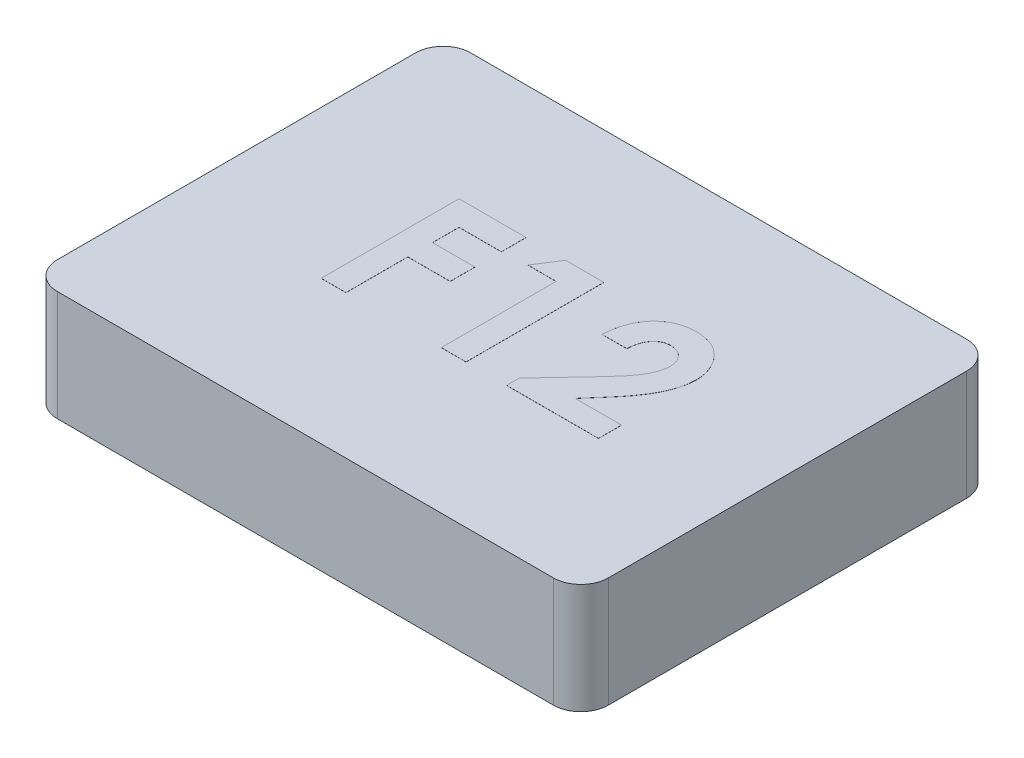
SolidWorks part; units mm, degrees
ref_plane "Front Plane" through (0, 0, 0) normal (0, 0, 1) x (1, 0, 0)
ref_plane "Top Plane" through (0, 0, 0) normal (0, 1, 0) x (1, 0, 0)
ref_plane "Right Plane" through (0, 0, 0) normal (1, 0, 0) x (0, 0, -1)
sketch "Sketch1" plane through (0, 0, 0) normal (0, 1, 0) x (1, 0, 0)
  line L0 (0, 0) -> (12.7, 0)
  line L1 (12.7, 0) -> (12.7, 9.525)
  line L2 (12.7, 9.525) -> (0, 9.525)
  line L3 (0, 9.525) -> (0, 0)
  dimension "D1" = 12.7
  dimension "D2" = 9.525
extrude "Boss-Extrude1" add sketch "Sketch1" along normal blind 2.54
fillet "Fillet1" radius 0.635 4 edges at (0, 1.27, -9.525) (12.7, 1.27, -9.525) (12.7, 1.27, 0) (0, 1.27, 0)
shell "Shell1" thickness 0.635 removed face at (6.35, 0, -4.7625)
sketch "Sketch2" plane through (0, 1.905, 0) normal (0, -1, 0) x (-1, 0, 0)
  line L0 (-0.635, 4.7625) -> (-12.065, 4.7625) construction
  line L1 (-0.635, 8.89) -> (-0.635, 0.635) construction
  line L2 (-12.065, 0.635) -> (-12.065, 8.89) construction
  line L3 (-6.35, 0.635) -> (-6.35, 8.89) construction
  line L4 (-0.635, 0.635) -> (-12.065, 0.635) construction
  line L5 (-12.065, 8.89) -> (-0.635, 8.89) construction
  circle A0 centre (-6.35, 4.7625) radius 2.54
  dimension "D1" = 5.08
extrude "Boss-Extrude2" add sketch "Sketch2" along normal up to surface (1.905 mm away) up to face at (6.35, 0, -4.7625)
sketch "Sketch3" plane through (0, 2.54, 0) normal (0, 1, 0) x (1, 0, 0)
  line L0 (0.635, 0) -> (12.065, 0) construction
  line L1 (0, 8.89) -> (0, 0.635) construction
  text T0 "<b>F12</b>"
  dimension "D1" = 3.302
  dimension "D2" = 3.048
extrude "Boss-Extrude3" add sketch "Sketch3" along normal blind 0.0025
